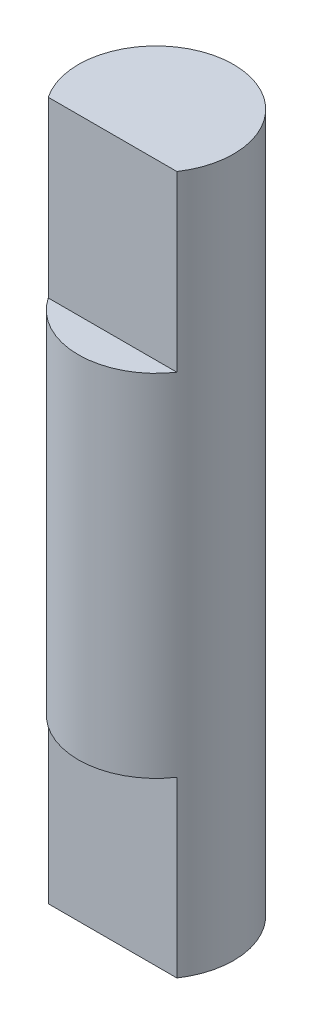
SolidWorks part; units mm, degrees
ref_plane "Front Plane" through (0, 0, 0) normal (0, 0, 1) x (1, 0, 0)
ref_plane "Top Plane" through (0, 0, 0) normal (0, 1, 0) x (1, 0, 0)
ref_plane "Right Plane" through (0, 0, 0) normal (1, 0, 0) x (0, 0, -1)
sketch "Sketch1" plane through (0, 0, 0) normal (0, 1, 0) x (1, 0, 0)
  circle A0 centre (0, 0) radius 3.175
  dimension "D1" = 6.35
extrude "Boss-Extrude1" add sketch "Sketch1" along normal blind 28.575
sketch "Sketch2" plane through (0, 28.575, 0) normal (0, 1, 0) x (1, 0, 0)
  line L0 (0, 0) -> (-2.6305, -1.778) construction
  line L1 (-2.6305, -1.778) -> (2.6305, -1.778)
  line L2 (2.6305, -1.778) -> (0, 0) construction
  line L3 (0, 0) -> (0, -1.778) construction
  line L4 (2.6305, -1.778) -> (2.7779, -3.6892)
  line L5 (2.7779, -3.6892) -> (-2.6305, -3.6892)
  line L6 (-2.6305, -3.6892) -> (-2.6305, -1.778)
  circle A0 centre (0, 0) radius 3.175 construction
  dimension "D1" = 1.778
extrude "Cut-Extrude1" cut sketch "Sketch2" against normal blind 7.112
sketch "Sketch3" plane through (0, 0, 0) normal (0, -1, 0) x (1, 0, 0)
  line L0 (0, 0) -> (-2.6305, 1.778) construction
  line L1 (-2.6305, 1.778) -> (2.6305, 1.778)
  line L2 (2.6305, 1.778) -> (0, 0) construction
  line L3 (0, 0) -> (0, 1.778) construction
  line L4 (-2.6305, 1.778) -> (-3.6008, 3.8742)
  line L5 (-3.6008, 3.8742) -> (2.4914, 4.8441)
  line L6 (2.4914, 4.8441) -> (2.6305, 1.778)
  circle A0 centre (0, 0) radius 3.175 construction
  dimension "D1" = 1.778
extrude "Cut-Extrude2" cut sketch "Sketch3" against normal blind 7.112
